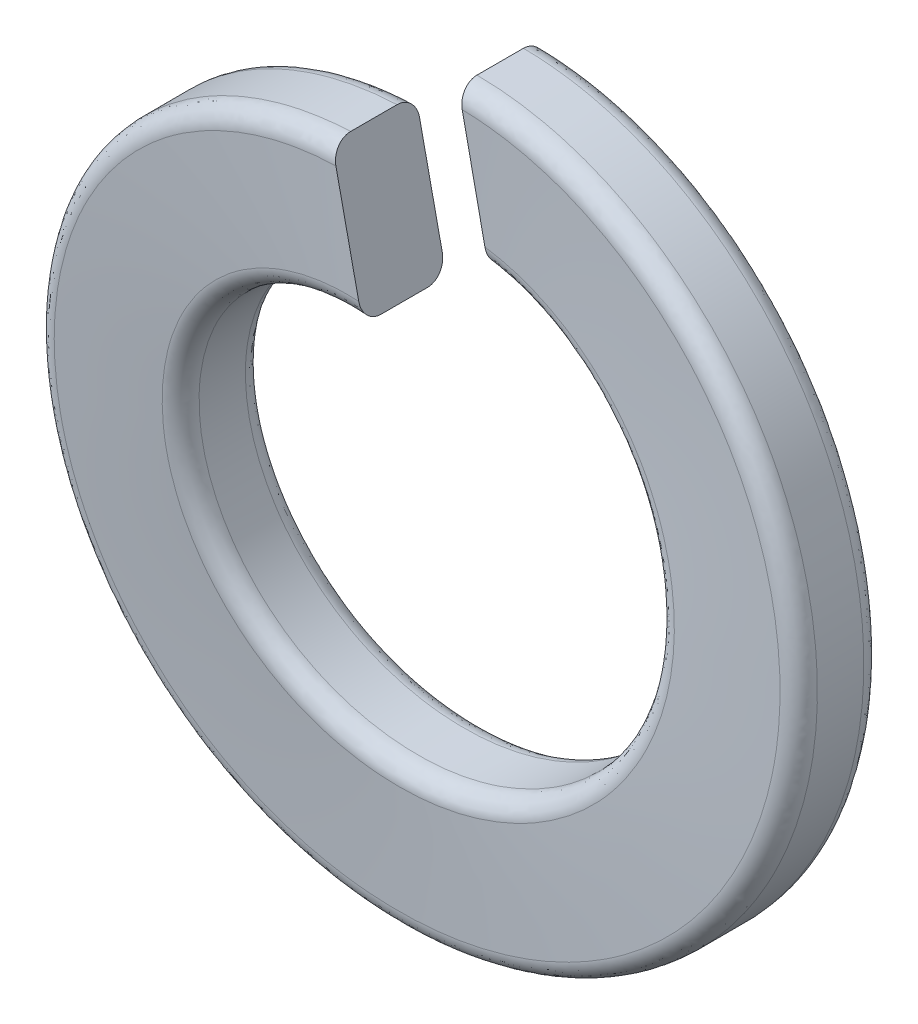
SolidWorks part; units mm, degrees
note: '?' marks a value the reader was unsure of.
ref_plane "Front Plane" through (0, 0, 0) normal (0, 0, 1) x (1, 0, 0)
ref_plane "Top Plane" through (0, 0, 0) normal (0, 1, 0) x (1, 0, 0)
ref_plane "Right Plane" through (0, 0, 0) normal (1, 0, 0) x (0, 0, -1)
sketch "Sketch1" plane through (0, 0, 0) normal (0, 0, 1) x (1, 0, 0)
  line L0 (0, -3.8) -> (0, 3.8) construction
  line L1 (-0.1658, 3.7964) -> (0.1692, 2.2436) construction
  line L2 (0, 0) -> (-1.125, -1.9486) construction
  line L3 (0, 2.25) -> (-0.3312, 3.7855) construction
  line L4 (0, 0) -> (-0.3312, 3.7855) construction
  line L5 (-0.1658, 3.7964) -> (0, 0) construction
  circle A0 centre (0, 0) radius 3.8 construction
  circle A1 centre (0, 0) radius 2.25 construction
  point P6 (0, -2.25)
  dimension "ID" = 4.5
  dimension "OD" = 7.6
  dimension "D2" = 5
  dimension "D1" = 30
  dimension "D3" = 2.5
sketch "Sketch2" plane through (0, 0, 0) normal (1, 0, 0) x (0, 0, -1)
  line L0 (-1.05, 0) -> (1.05, 0) construction
  line L1 (0, -3.8) -> (0, 3.8) construction
  line L2 (-1.05, 3.8) -> (-0.15, 3.8) construction
  line L3 (-1.05, 3.8) -> (-1.05, 2.25) construction
  line L4 (-1.05, 2.25) -> (-0.15, 2.25) construction
  line L5 (-0.15, 3.8) -> (-0.15, 2.25) construction
  line L6 (0, -3.8) -> (0, 3.8) construction
  line L12 (-0.45, -2.25) -> (0.45, -2.25) construction
  line L13 (-0.45, -2.25) -> (-0.45, -3.8) construction
  line L14 (-0.45, -3.8) -> (0.45, -3.8) construction
  line L15 (0.45, -2.25) -> (0.45, -3.8) construction
  point P8 (-0.6, 3.8)
  point P13 (0.45, -3.6)
  point P15 (1.05, 3.8)
  point P19 (0.6, 3.8)
  dimension "Thickness" = 0.9
  dimension "Helix Height" = 1.2
  dimension "Height" = 2.1
  dimension "Radius" = 0.2
ref_plane "Plane1" through (0, 0, 0.6) normal (0, 0, 1) x (1, 0, 0)
sketch "Sketch3" plane through (0, 0, 0.6) normal (0, 0, 1) x (1, 0, 0)
  circle A0 centre (0, 0) radius 3.8 construction
  circle A1 centre (0, 0) radius 3.8
curve "Helix/Spiral1" pitch 1.2012 height 1.2 turns 0.999
ref_plane "Plane2" through (0.4637, 0.1, 0) normal (0.9775, 0.2108, 0) x (0.0074, -0.0342, -0.9994)
sketch "Sketch4" plane through (0.4942, -0.0415, 0.0051) normal (0.9775, 0.2108, 0) x (0.0074, -0.0342, -0.9994)
  line L0 (-1.1793, 3.8204) -> (-0.2798, 3.8519) construction
  line L10 (-1.1263, 2.3062) -> (-0.2268, 2.3376) construction
  line L12 (-1.1812, 3.8761) -> (-0.2818, 3.9075)
  line L13 (-0.2818, 3.9075) -> (-0.2268, 2.3376)
  line L14 (-1.1263, 2.3062) -> (-0.2268, 2.3376)
  line L15 (-1.1812, 3.8761) -> (-1.1263, 2.3062)
sweep "Sweep1" add profiles "Sketch4" path "Helix/Spiral1"
sketch "Sketch5" plane through (0, 0, 0) normal (0, 0, 1) x (1, 0, 0)
  line L0 (0, 2.25) -> (-0.3312, 3.7855) construction
  line L1 (-0.1658, 3.7964) -> (0.1692, 2.2436) construction
  line L2 (0, 2.25) -> (-0.3312, 3.7855)
  line L3 (-0.1658, 3.7964) -> (0.1692, 2.2436)
  circle A0 centre (0, 0) radius 2.25 construction
  circle A1 centre (0, 0) radius 3.8 construction
  arc A2 (0.1692, 2.2436) -> (0, 2.25) centre (0, 0) ccw
  arc A3 (-0.1658, 3.7964) -> (-0.3312, 3.7855) centre (0, 0) ccw
extrude "Cut-Extrude1" cut sketch "Sketch5" against normal through all
fillet "Fillet1" radius 0.2 4 edges
ref_axis "Center Axis 1" through (0, 0, 1.05) along (0, 0, -1)?
ref_plane "Contact Plane 1" through (0, 0, 1.05) normal (0, 0, 1) x (1, 0, 0)
ref_plane "Contact Plane 2" through (0, 0, -1.05) normal (0, 0, 1) x (1, 0, 0)
equation "\"D3@Helix/Spiral1\"=\"Helix Height@Sketch2\""
equation "\"D7@Helix/Spiral1\"=90+\"D2@Sketch1\""
equation "\"D1@Fillet1\"=\"Radius@Sketch2\""
equation "\"D3@Sketch1\"=\"D2@Sketch1\"/2"
